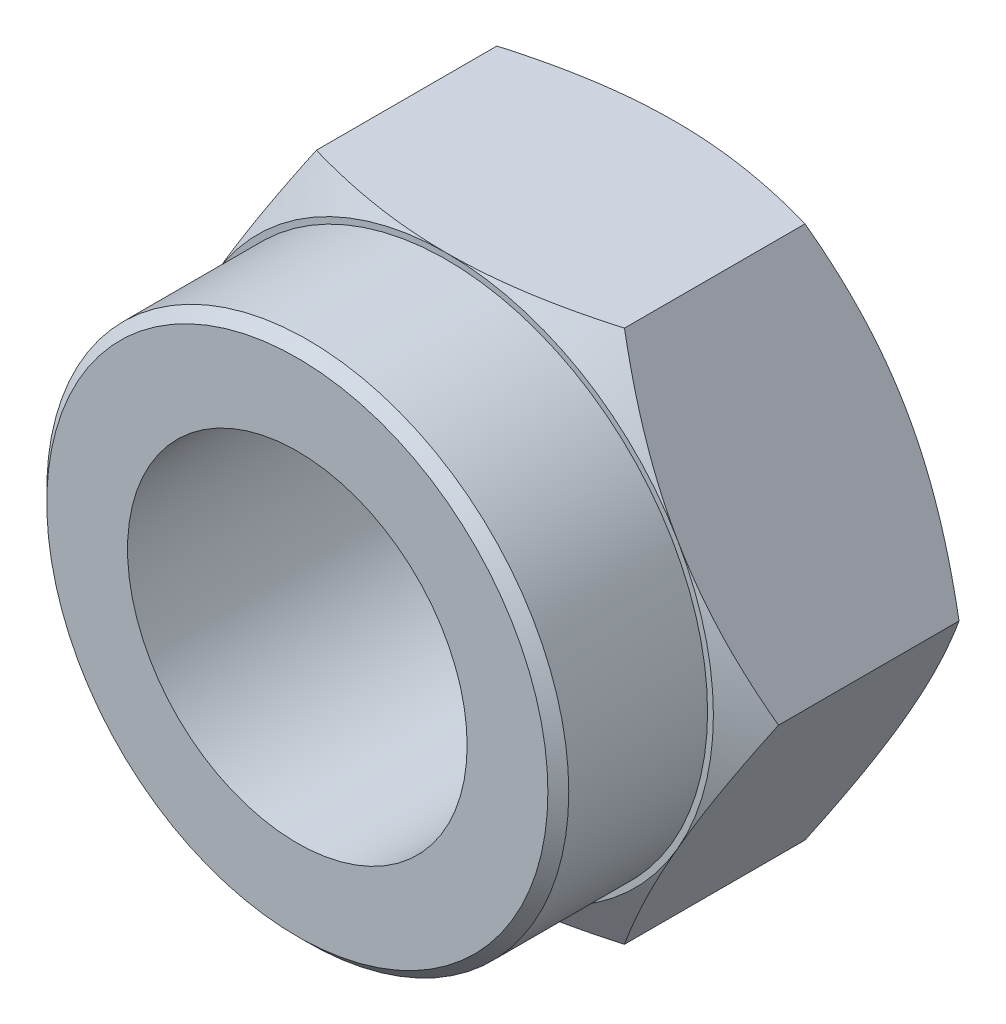
SolidWorks part; units mm, degrees
ref_plane "Front" through (0, 0, 0) normal (0, 0, 1) x (1, 0, 0)
ref_plane "Top" through (0, 0, 0) normal (0, 1, 0) x (1, 0, 0)
ref_plane "Right" through (0, 0, 0) normal (1, 0, 0) x (0, 0, -1)
sketch "Sketch1" plane through (0, 0, 0) normal (0, 0, 1) x (1, 0, 0)
  line L1 (15.8771, -27.5) -> (31.7543, 0)
  line L2 (31.7543, 0) -> (15.8771, 27.5)
  line L3 (15.8771, 27.5) -> (-15.8771, 27.5)
  line L4 (-15.8771, 27.5) -> (-31.7543, 0)
  line L5 (-31.7543, 0) -> (-15.8771, -27.5)
  line L6 (-15.8771, -27.5) -> (15.8771, -27.5)
  circle A0 centre (0, 0) radius 27.5 construction
  circle A1 centre (0, 0) radius 17.5
extrude "BaseNut" add sketch "Sketch1" against normal blind 23.52
cosmetic thread "ThreadCosmetic1" [suppressed] parameters "m"=29.4, "D2"=36
sketch "Sketch3" plane through (0, 0, 0) normal (0, 1, 0) x (1, 0, 0)
  line L0 (0, 16.3108) -> (0, -16.1137) construction
  line L2 (-2.0696, 11.76) -> (33.5085, 11.76) construction
  line L3 (27.5, 23.52) -> (31.7543, 23.52)
  line L5 (31.7543, 23.52) -> (31.7543, 21.0638)
  line L7 (31.7543, 21.0638) -> (27.5, 23.52)
  line L8 (31.7543, 2.4562) -> (27.5, 0)
  line L9 (31.7543, 0) -> (31.7543, 2.4562)
  line L10 (27.5, 0) -> (31.7543, 0)
  dimension "D1" = 30
  dimension "s1" = 55
revolve "Double-Chamfer" cut sketch "Sketch3" angle 360 about L0
sketch "Sketch2" plane through (19.1814, 9.5168, 0) normal (0, 0, 1) x (1, 0, 0)
  circle A1 centre (-19.1814, -9.5168) radius 17.5 construction
  circle A2 centre (-19.1814, -9.5168) radius 26.9
  circle A3 centre (-19.1814, -9.5168) radius 17.5
extrude "Extrude1" add sketch "Sketch2" along normal offset from surface (15.38 mm away) 38.9 up to face at (17.5, 0, -23.52)
sketch "Sketch5" plane through (0, 0, 0) normal (0, 1, 0) x (1, 0, 0)
  line L0 (0, 16.8008) -> (0, -2.8116) construction
  line L2 (17.5, 23.52) -> (19.45, 23.52)
  line L5 (19.45, 23.52) -> (17.5, 22.3942)
  line L7 (17.5, 22.3942) -> (17.5, 23.52)
  dimension "D1" = 30
  dimension "da" = 38.9
revolve "EndChamfer" cut sketch "Sketch5" angle 360 about L0
chamfer "Chamfer1" distance 1.076 angle 45 1 edges at (26.9, 0, 15.38)
sketch "Sketch6" plane through (0, 0, 0) normal (0, 1, 0) x (1, 0, 0)
  line L0 (0, -21.8676) -> (0, 36.2739) construction
  line L1 (-17.933, 22.3942) -> (-17.5, 22.1442)
  line L2 (-17.5, 22.1442) -> (-17, 22.1442)
  line L3 (-17, 22.1442) -> (-17, 22.6442)
  line L4 (-17, 22.6442) -> (-17.5, 22.6442)
  line L5 (-17.5, 22.6442) -> (-17.933, 22.3942)
  dimension "D1" = 0.5
  dimension "D2" = 35
revolve "Cut-Revolve10" [suppressed] cut sketch "Sketch6" angle 360 about L0
pattern_linear "LPattern10" [suppressed] count 39 spacing 0.6 along (0, 0, 1) of bodies 105
equation "\"D1@Chamfer1\" = \"s1@Sketch2\" / 50"
equation "\"s1@Sketch3\" = \"s@Sketch1\""
equation "\"D2@Sketch6\" = \"xd@Sketch1\""
equation "\"D1@Sketch6\" =  ( \"D2@ThreadCosmetic1\"  - \"xd@Sketch1\")  / 2"
equation "\"D3@LPattern10\" = \"D1@Sketch6\" * 1.2"
equation "\"D1@LPattern10\" = \"m@BaseNut\" / \"D3@LPattern10\""
